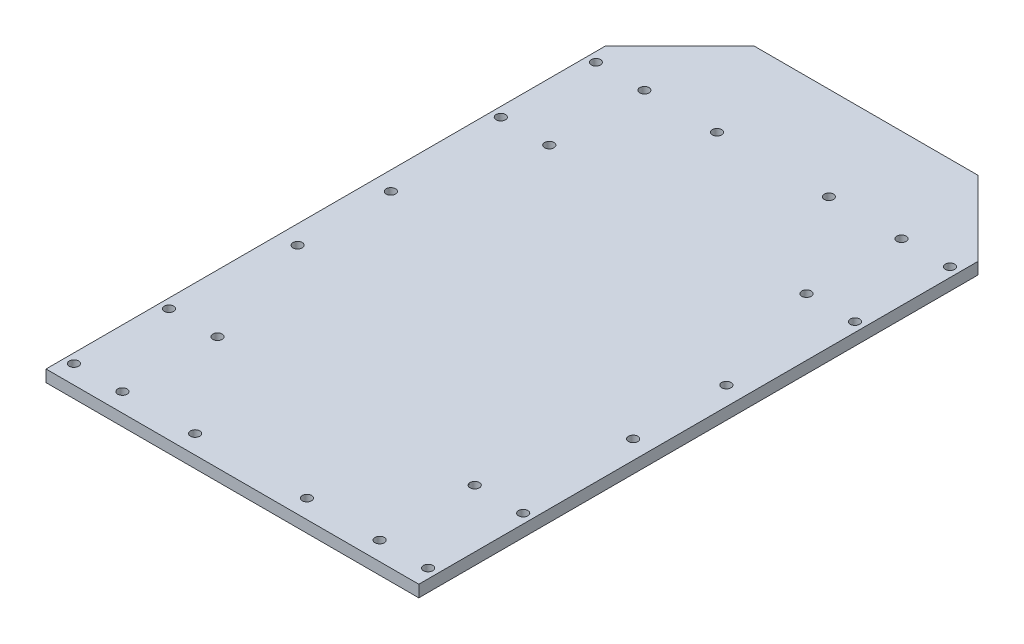
SolidWorks part; units mm, degrees
ref_plane "Front Plane" through (0, 0, 0) normal (0, 0, 1) x (1, 0, 0)
ref_plane "Top Plane" through (0, 0, 0) normal (0, 1, 0) x (1, 0, 0)
ref_plane "Right Plane" through (0, 0, 0) normal (1, 0, 0) x (0, 0, -1)
sketch "Sketch1" plane through (0, 0, 0) normal (0, 1, 0) x (1, 0, 0)
  line L0 (-200, 300) -> (-160, 340)
  line L1 (0, 0) -> (-200, 0)
  line L2 (0, 0) -> (0, 300)
  line L3 (0, 300) -> (-200, 300)
  line L4 (-200, 0) -> (-200, 300)
  line L5 (-160, 340) -> (-40, 340)
  line L6 (-40, 340) -> (0, 300)
  line L7 (-195, 290) -> (-169, 290) construction
  line L8 (-195, 239) -> (-169, 239) construction
  line L9 (-195, 290) -> (-195, 239) construction
  line L10 (-195, 290) -> (-200, 290) construction
  line L11 (-100, 300) -> (-100, 0) construction
  line L12 (-200, 150) -> (0, 150) construction
  circle A0 centre (-195, 290) radius 2.5
  circle A1 centre (-169, 290) radius 2.5
  circle A2 centre (-195, 239) radius 2.5
  circle A3 centre (-169, 239) radius 2.5
  circle A4 centre (-31, 290) radius 2.5
  circle A5 centre (-5, 290) radius 2.5
  circle A6 centre (-5, 239) radius 2.5
  circle A7 centre (-31, 239) radius 2.5
  circle A8 centre (-5, 10) radius 2.5
  circle A9 centre (-5, 61) radius 2.5
  circle A10 centre (-31, 61) radius 2.5
  circle A11 centre (-31, 10) radius 2.5
  circle A12 centre (-169, 10) radius 2.5
  circle A13 centre (-169, 61) radius 2.5
  circle A14 centre (-195, 10) radius 2.5
  circle A15 centre (-195, 61) radius 2.5
  dimension "D9" = 5
  dimension "D1" = 45
  dimension "D2" = 40
  dimension "D3" = 300
  dimension "D4" = 200
  dimension "D5" = 51
  dimension "D6" = 26
  dimension "D7" = 5
  dimension "D8" = 10
extrude "Boss-Extrude1" add sketch "Sketch1" along normal blind 6.35 contours L4 L1 L2 L3 | L6 L5 L0 L3 region at (-100, 0, -318.3333) region at (-100, 0, -150)
sketch "Sketch2" plane through (0, 6.35, 0) normal (0, 1, 0) x (1, 0, 0)
  line L0 (-100, 0) -> (-100, 50000) construction
  line L1 (0, 0) -> (-200, 0) construction
  line L2 (-160, 340) -> (-40, 340) construction
  line L3 (-145, 150) -> (49855, 150) construction
  line L4 (-200, 0) -> (-200, 300) construction
  line L5 (0, 0) -> (0, 300) construction
  circle A0 centre (-70, 10) radius 2.5
  circle A2 centre (-10, 125) radius 2.5
  circle A3 centre (-190, 125) radius 2.5
  circle A4 centre (-130, 10) radius 2.5
  circle A5 centre (-70, 290) radius 2.5
  circle A6 centre (-10, 175) radius 2.5
  circle A7 centre (-190, 175) radius 2.5
  circle A8 centre (-130, 290) radius 2.5
  point P4 (-100, 0)
  point P7 (-100, 340)
  point P12 (-200, 150)
  point P15 (0, 150)
  dimension "D1" = 5
  dimension "D2" = 10
  dimension "D3" = 30
  dimension "D4" = 10
  dimension "D5" = 25
extrude "Cut-Extrude1" cut sketch "Sketch2" against normal blind 10
